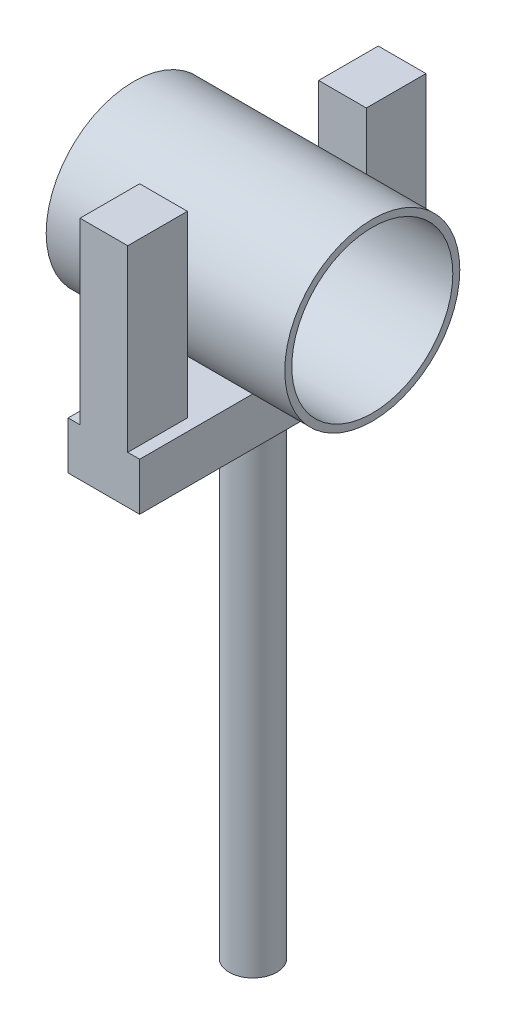
SolidWorks part; units mm, degrees
ref_plane "Front Plane" through (0, 0, 0) normal (0, 0, 1) x (1, 0, 0)
ref_plane "Top Plane" through (0, 0, 0) normal (0, 1, 0) x (1, 0, 0)
ref_plane "Right Plane" through (0, 0, 0) normal (1, 0, 0) x (0, 0, -1)
sketch "Sketch1" plane through (0, 0, 0) normal (0, 1, 0) x (1, 0, 0)
  circle A0 centre (0, 0) radius 10
  dimension "D1" = 20
extrude "Boss-Extrude1" add sketch "Sketch1" along normal blind 200
sketch "Sketch2" plane through (0, 0, 0) normal (1, 0, 0) x (0, 0, -1)
  line L0 (0, 200) -> (0, 210) construction
  line L1 (10, 200) -> (-10, 200) construction
  line L3 (-62.5, 220) -> (62.5, 220)
  line L4 (-62.5, 220) -> (-62.5, 200)
  line L5 (-62.5, 200) -> (62.5, 200)
  line L6 (62.5, 220) -> (62.5, 200)
  line L7 (-62.5, 220) -> (62.5, 200) construction
  line L8 (-62.5, 200) -> (62.5, 220) construction
  dimension "D1" = 10
  dimension "D2" = 125
extrude "Boss-Extrude2" add sketch "Sketch2" along normal blind 15 and the other way blind 15
sketch "Sketch3" plane through (0, 0, 0) normal (1, 0, 0) x (0, 0, -1)
  line L1 (-62.5, 220) -> (-37.5, 220)
  line L2 (-62.5, 220) -> (-62.5, 295)
  line L3 (-62.5, 295) -> (-37.5, 295)
  line L4 (-37.5, 220) -> (-37.5, 295)
  line L5 (62.5, 220) -> (37.5, 220)
  line L6 (62.5, 220) -> (62.5, 295)
  line L7 (62.5, 295) -> (37.5, 295)
  line L8 (37.5, 220) -> (37.5, 295)
  dimension "D1" = 25
  dimension "D2" = 75
  dimension "D3" = 75
  dimension "D4" = 25
extrude "Boss-Extrude3" add sketch "Sketch3" along normal blind 10 and the other way blind 10
sketch "Sketch4" plane through (0, 0, 0) normal (1, 0, 0) x (0, 0, -1)
  line L0 (0, 220) -> (0, 293.3743) construction
  line L1 (62.5, 220) -> (-62.5, 220) construction
  line L2 (-37.5, 257.5) -> (37.5, 257.5) construction
  line L3 (-37.5, 220) -> (-37.5, 295) construction
  line L4 (37.5, 295) -> (37.5, 220) construction
  circle A0 centre (0, 256.6872) radius 36.6872
  dimension "D1" = 73.3743
extrude "Boss-Extrude4" add sketch "Sketch4" along normal blind 50 and the other way blind 50 separate body
sketch "Sketch5" plane through (50, 0, 0) normal (1, 0, 0) x (0, 0, -1)
  circle A0 centre (0, 256.6872) radius 33.75
  dimension "D1" = 67.5
extrude "Cut-Extrude2" cut sketch "Sketch5" against normal blind 95
ref_axis "Axis1" through (0, 200, 0) along (0, -1, 0)
ref_plane "Plane1" through (0, 100, 0) normal (0, 1, 0) x (1, 0, 0)
ref_axis "Axis2" through (0, 100, 68.75) along (0, 0, -1)
